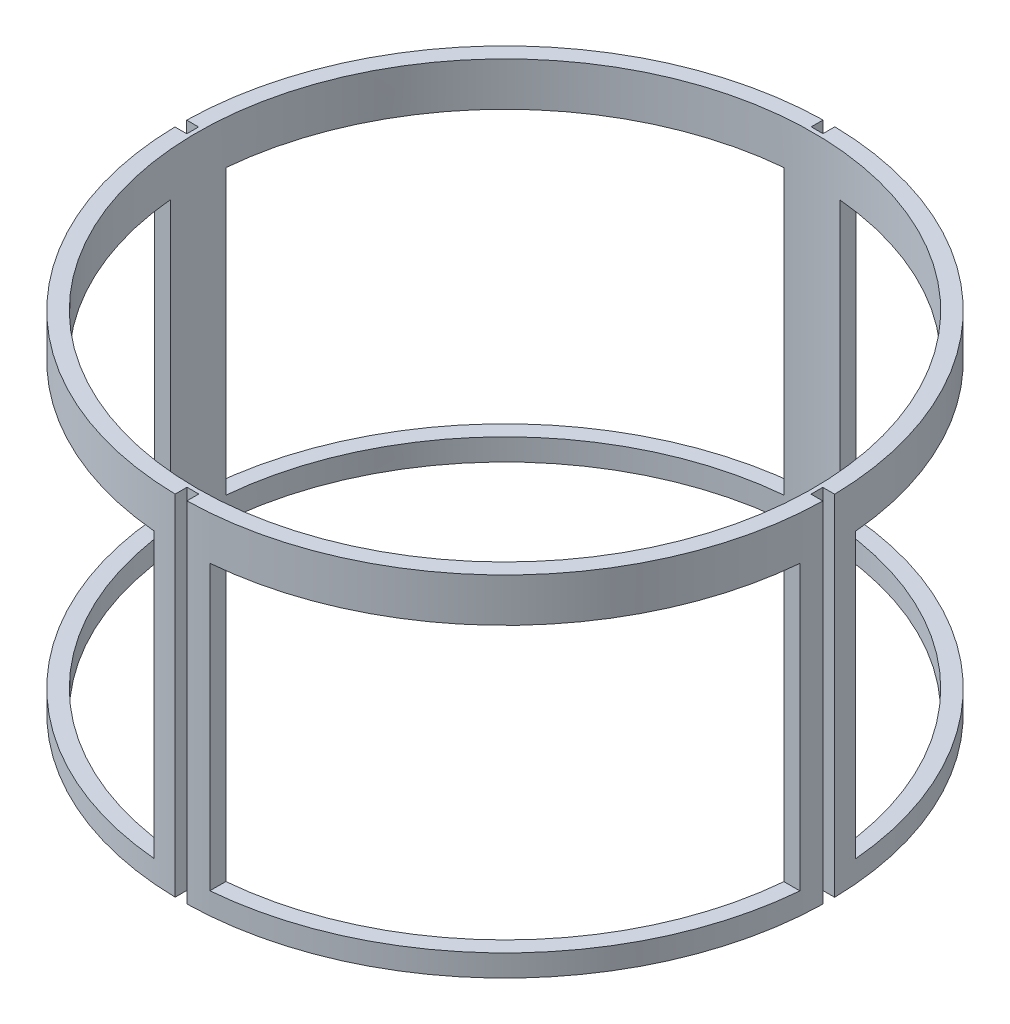
SolidWorks part; units mm, degrees
ref_plane "Front" through (0, 0, 0) normal (0, 0, 1) x (1, 0, 0)
ref_plane "Top" through (0, 0, 0) normal (0, 1, 0) x (1, 0, 0)
ref_plane "Right" through (0, 0, 0) normal (1, 0, 0) x (0, 0, -1)
sketch "Sketch1" plane through (0, 0, 0) normal (0, 1, 0) x (1, 0, 0)
  circle A0 centre (0, 0) radius 89.662
  circle A1 centre (0, 0) radius 94.2975
  dimension "Inner Diameter" = 179.324
  dimension "Outer Diameter" = 188.595
extrude "Boss-Extrude1" add sketch "Sketch1" against normal blind 101.6
sketch "Sketch5" plane through (0, 0, 0) normal (0, 1, 0) x (1, 0, 0)
  line L0 (0, 114.2751) -> (0, -136.7211) construction
  line L1 (-124.857, 0) -> (116.4345, 0) construction
  line L2 (-1.7145, 90.8209) -> (1.7145, 90.8209)
  line L3 (1.7145, 90.8209) -> (1.7145, 95.9009)
  line L4 (1.7145, 95.9009) -> (-1.7145, 95.9009)
  line L5 (-1.7145, 95.9009) -> (-1.7145, 90.8209)
  line L6 (1.7145, -95.9009) -> (-1.7145, -95.9009)
  line L7 (1.7145, -90.8209) -> (1.7145, -95.9009)
  line L8 (-1.7145, -90.8209) -> (1.7145, -90.8209)
  line L9 (-1.7145, -95.9009) -> (-1.7145, -90.8209)
  line L10 (-90.8209, 1.651) -> (-90.8209, -1.778)
  line L11 (-90.8209, -1.778) -> (-95.9009, -1.778)
  line L12 (-95.9009, -1.778) -> (-95.9009, 1.651)
  line L13 (-95.9009, 1.651) -> (-90.8209, 1.651)
  line L14 (95.9009, -1.778) -> (95.9009, 1.651)
  line L15 (90.8209, -1.778) -> (95.9009, -1.778)
  line L16 (90.8209, 1.651) -> (90.8209, -1.778)
  line L17 (95.9009, 1.651) -> (90.8209, 1.651)
  dimension "D1" = 1.7145
  dimension "D2" = 1.7145
  dimension "D3" = 5.08
  dimension "D4" = 90.8209
  dimension "D5" = 1.651
  dimension "D6" = 90.8209
extrude "Cut-Extrude1" cut sketch "Sketch5" against normal blind 101.6
sketch "Sketch7" plane through (0, 0, 0) normal (0, 1, 0) x (1, 0, 0)
  line L0 (89.2928, -8.128) -> (93.9465, -8.128)
  line L1 (8.0645, -89.2986) -> (8.0645, -93.952)
  line L2 (1.7145, -94.2819) -> (1.7145, -90.8209) construction
  line L3 (90.8209, -1.778) -> (94.2807, -1.778) construction
  arc A0 (89.2928, -8.128) -> (8.0645, -89.2986) centre (0, 0) cw
  circle A1 centre (0, 0) radius 89.662 construction
  arc A2 (93.9465, -8.128) -> (8.0645, -93.952) centre (0, 0) cw
  arc A3 (1.7145, -94.2819) -> (94.2807, -1.778) centre (0, 0) ccw construction
  point P15 (92.5508, -1.778)
  dimension "D3" = 94.2975
  dimension "D4" = 89.662
  dimension "D1" = 6.35
  dimension "D2" = 6.35
extrude "Cut-Extrude2" cut sketch "Sketch7" against normal blind 82.55 from offset 12.7 offset against normal yes
pattern_circular "CirPattern1" count 4 over 360 about axis through (0, 0, 0) along (0, 1, 0) of "Cut-Extrude2"
equation "\"D4@Sketch5\"=(\"Inner Diameter\"/2)+((\"Outer Diameter\"-\"Inner Diameter\")/8)"
equation "\"D6@Sketch5\"=(\"Inner Diameter\"/2)+((\"Outer Diameter\"-\"Inner Diameter\")/8)"
equation "\"D1@Cut-Extrude1\"=\"Fin Length\""
equation "\"D3@Sketch7\"=\"Outer Diameter\"/2"
equation "\"D4@Sketch7\"=\"Inner Diameter\"/2"
